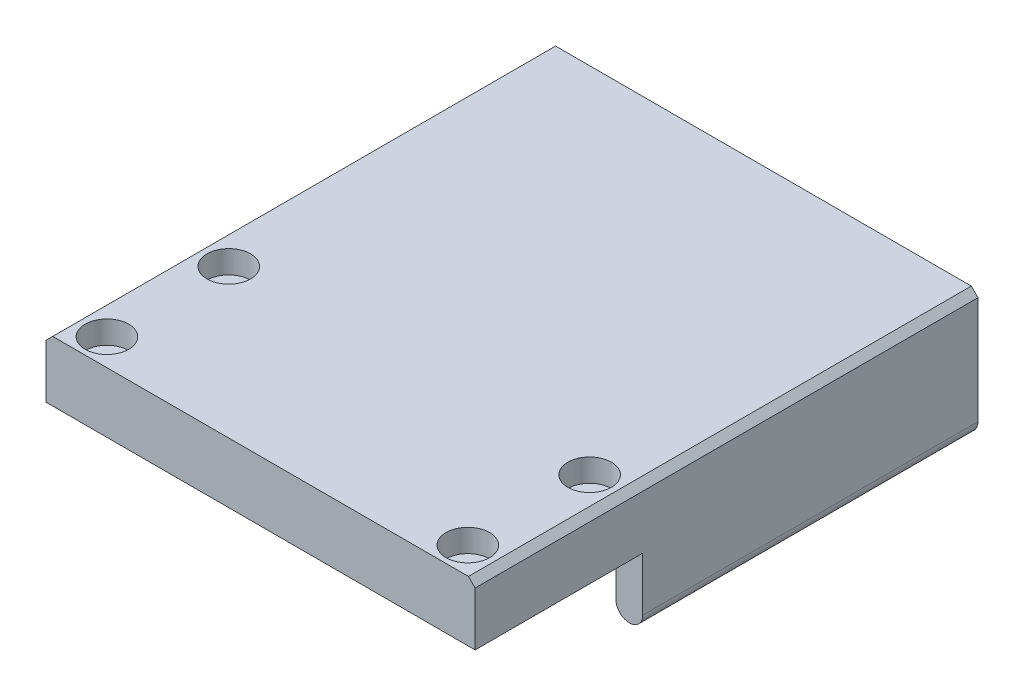
SolidWorks part; units mm, degrees
ref_plane "Front Plane" through (0, 0, 0) normal (0, 0, 1) x (1, 0, 0)
ref_plane "Top Plane" through (0, 0, 0) normal (0, 1, 0) x (1, 0, 0)
ref_plane "Right Plane" through (0, 0, 0) normal (1, 0, 0) x (0, 0, -1)
sketch "Sketch1" plane through (0, 0, 0) normal (0, 1, 0) x (1, 0, 0)
  line L0 (32, -75) -> (-32, -75)
  line L1 (0, -75) -> (0, -150) construction
  line L2 (32, -150) -> (-32, -150)
  line L3 (-32, -150) -> (-32, -75)
  line L4 (32, -150) -> (32, -75)
  point P7 (0, 0)
  dimension "\"neck length" = 75
extrude "Boss-Extrude1" add sketch "Sketch1" along normal blind 19
shell "Shell1" thickness 4 removed face at (0, 0, 112.5)
fillet "Fillet2" 2 edges at (32, 0, 112.5) (28, 0, 112.5) type full round first side face at (32, 9.5, 112.5) second side face at (28, 5, 112.5) middle face at (0, 0, 112.5)
fillet "Fillet3" 2 edges at (-32, 0, 112.5) (-28, 0, 112.5) type full round first side face at (-32, 9.5, 112.5) second side face at (-28, 5, 112.5) middle face at (0, 0, 112.5)
chamfer "Chamfer1" distance 1 angle 45 2 edges at (32, 19, 112.5) (-32, 19, 112.5)
sketch "Sketch7" plane through (0, 0, 150) normal (0, 0, 1) x (1, 0, 0)
  line L1 (-32, 10) -> (32, 10)
  line L2 (-32, 18) -> (-32, 2) construction
  line L3 (32, 18) -> (32, 2) construction
  line L4 (32, 10) -> (32, 0)
  line L7 (-32, 0) -> (-32, 10)
  line L8 (-32, 0) -> (32, 0)
extrude "Cut-Extrude3" cut sketch "Sketch7" against normal blind 25
hole_wizard "CBORE for M3 Hex Socket Head Cap Screw1" positions "Sketch12" profile "Sketch13" counterbore size "M3" standard "ISO" end condition through all
sketch "Sketch12" plane through (75.2969, 19, 61.2992) normal (0, 1, 0) x (1, 0, 0)
  point P0 (-102.2096, -66.5318)
  point P1 (-102.2096, -84.7008)
  point P2 (-48.3841, -84.7008)
  point P3 (-48.3841, -66.5318)
sketch "Sketch13" plane through (-26.9127, 19, 127.831) normal (1, 0, 0) x (0, 0, 1)
  line L0 (0, 0) -> (0, 19)
  line L1 (0, 19) -> (1.45, 19)
  line L2 (1.45, 19) -> (1.45, 3.4)
  line L3 (1.45, 3.4) -> (3.25, 3.4)
  line L4 (3.25, 3.4) -> (3.25, 0)
  line L5 (3.25, 0) -> (0, 0)
  line L6 (0, -6.35) -> (0, 107.95) construction
  dimension "Thru Hole Dia." = 2.9
  dimension "Thru Hole Depth" = 19
  dimension "C'Bore Dia." = 6.5
  dimension "C'Bore Depth" = 3.4
ref_plane "Plane1" through (0, 0, 100) normal (0, 0, 1) x (1, 0, 0)
equation "\"neck length\"= 200mm"
equation "\"stringLength\"=69.2489"
